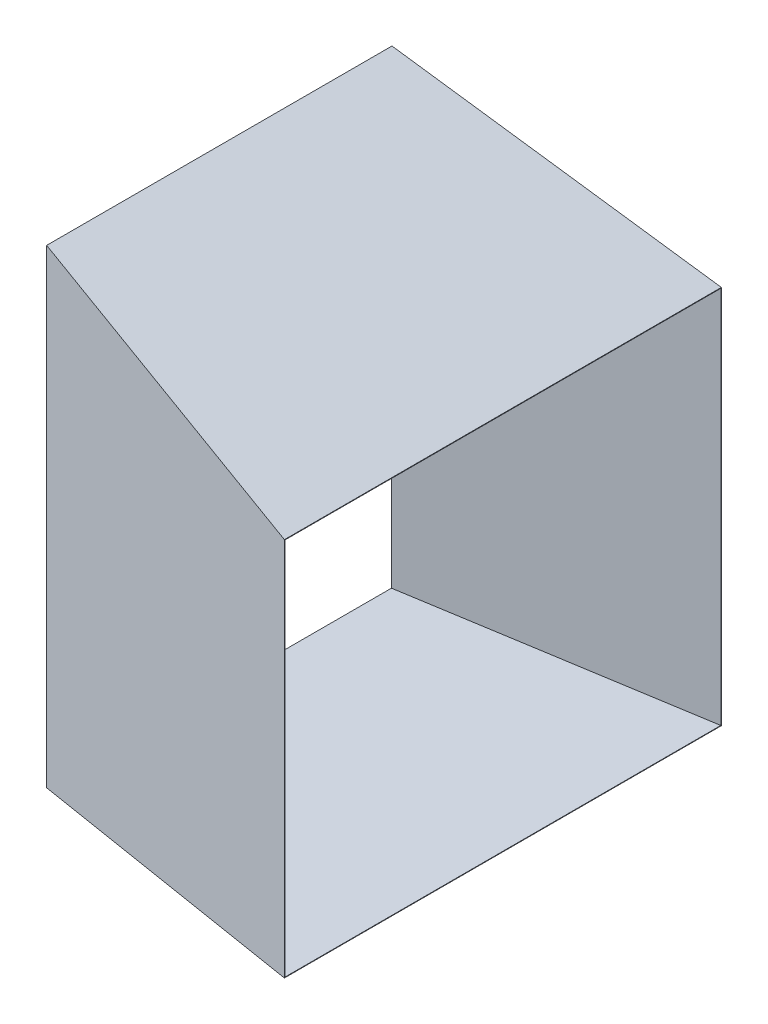
SolidWorks part; units mm, degrees
ref_plane "Front Plane" through (0, 0, 0) normal (0, 0, 1) x (1, 0, 0)
ref_plane "Top Plane" through (0, 0, 0) normal (0, 1, 0) x (1, 0, 0)
ref_plane "Right Plane" through (0, 0, 0) normal (1, 0, 0) x (0, 0, -1)
sketch "Sketch1" plane through (0, 0, 0) normal (0, 0, 1) x (1, 0, 0)
  line L0 (0, 0) -> (1349, 0)
  line L1 (1349, 1806) -> (1349, 0)
  line L2 (1349, 1806) -> (0, 2235)
  line L3 (0, 2235) -> (0, 0)
  dimension "D1" = 1349
  dimension "D2" = 2235
  dimension "D3" = 1806
extrude "Boss-Extrude1" add sketch "Sketch1" along normal blind 1039.25 and the other way blind 1039.25
sketch "Sketch2" plane through (0, 0, 0) normal (0, -1, 0) x (1, 0, 0)
  line L0 (0, 821.33) -> (0, 1039.25)
  line L1 (0, -1039.25) -> (0, 1039.25) construction
  line L2 (0, 1039.25) -> (1349, 1039.25)
  line L3 (1349, 1039.25) -> (0, 821.33)
  line L4 (0, 0) -> (-1860.8429, 0) construction
  line L5 (0, -1039.25) -> (1349, -1039.25)
  line L6 (0, -821.33) -> (0, -1039.25)
  line L7 (1349, -1039.25) -> (0, -821.33)
  dimension "D1" = 217.92
extrude "Cut-Extrude1" cut sketch "Sketch2" against normal blind 4942.25
shell "Shell2" thickness 2.5 removed face at (1349, 903, 0) removed face at (0, 1117.5, 0)
